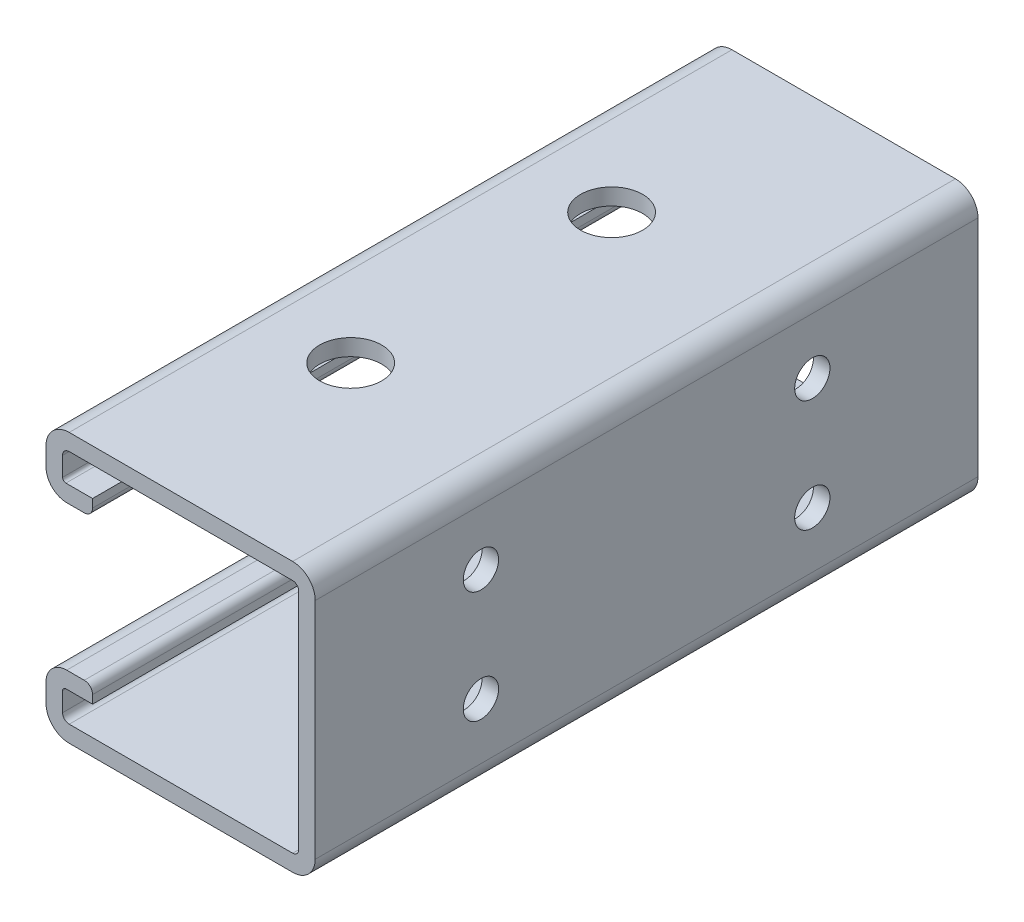
SolidWorks part; units mm, degrees
ref_plane "Front Plane" through (0, 0, 0) normal (0, 0, 1) x (1, 0, 0)
ref_plane "Top Plane" through (0, 0, 0) normal (0, 1, 0) x (1, 0, 0)
ref_plane "Right Plane" through (0, 0, 0) normal (1, 0, 0) x (0, 0, -1)
sketch "Sketch1" plane through (0, 0, 0) normal (0, 0, 1) x (1, 0, 0)
  line L0 (20.6375, 0) -> (-20.6375, 0) construction
  line L3 (-20.6375, 20.6375) -> (20.6375, 20.6375) construction
  line L4 (-20.6375, 20.6375) -> (-20.6375, -20.6375) construction
  line L5 (-20.6375, -20.6375) -> (20.6375, -20.6375) construction
  line L6 (20.6375, 20.6375) -> (20.6375, -20.6375) construction
  line L7 (-17.0815, 20.6375) -> (17.1768, 20.6375)
  line L8 (20.6375, 17.1767) -> (20.6375, -17.1767)
  line L9 (18.0975, -17.1767) -> (18.0975, 17.1767)
  line L10 (17.1768, 18.0975) -> (-17.0815, 18.0975)
  line L11 (-20.6375, 17.0815) -> (-20.6375, 14.2875)
  line L12 (-17.4625, 11.1125) -> (-14.7701, 11.1125)
  line L14 (-13.5001, 13.6525) -> (-17.5895, 13.6525)
  line L15 (-18.0975, 14.1605) -> (-18.0975, 17.0815)
  line L16 (-18.0975, -14.1605) -> (-18.0975, -17.0815)
  line L17 (-13.5001, -13.6525) -> (-17.5895, -13.6525)
  line L18 (-17.4625, -11.1125) -> (-14.7701, -11.1125)
  line L19 (-20.6375, -17.0815) -> (-20.6375, -14.2875)
  line L20 (17.1768, -18.0975) -> (-17.0815, -18.0975)
  line L21 (-17.0815, -20.6375) -> (17.1768, -20.6375)
  line L22 (18.0975, -20.6375) -> (18.0975, 20.6375) construction
  line L23 (-13.5001, 13.6525) -> (-13.5001, 12.3825)
  line L24 (-13.5001, 12.3825) -> (-13.5001, 11.1125) construction
  line L25 (-13.5001, -13.6525) -> (-13.5001, -12.3825)
  line L26 (0.0476, 18.0975) -> (0.0476, -18.0975) construction
  arc A1 (20.6375, 17.1767) -> (17.1768, 20.6375) centre (17.1768, 17.1767) ccw
  arc A2 (18.0975, 17.1767) -> (17.1768, 18.0975) centre (17.1768, 17.1767) ccw
  arc A4 (-17.0815, 20.6375) -> (-20.6375, 17.0815) centre (-17.0815, 17.0815) ccw
  arc A5 (-20.6375, 14.2875) -> (-17.4625, 11.1125) centre (-17.4625, 14.2875) ccw
  arc A6 (-13.5001, 12.3825) -> (-14.7701, 11.1125) centre (-14.7701, 12.3825) cw
  arc A7 (-17.5895, 13.6525) -> (-18.0975, 14.1605) centre (-17.5895, 14.1605) cw
  arc A8 (-18.0975, 17.0815) -> (-17.0815, 18.0975) centre (-17.0815, 17.0815) cw
  arc A9 (-18.0975, -17.0815) -> (-17.0815, -18.0975) centre (-17.0815, -17.0815) ccw
  arc A10 (-17.5895, -13.6525) -> (-18.0975, -14.1605) centre (-17.5895, -14.1605) ccw
  arc A11 (-13.5001, -12.3825) -> (-14.7701, -11.1125) centre (-14.7701, -12.3825) ccw
  arc A12 (-20.6375, -14.2875) -> (-17.4625, -11.1125) centre (-17.4625, -14.2875) cw
  arc A13 (-17.0815, -20.6375) -> (-20.6375, -17.0815) centre (-17.0815, -17.0815) cw
  arc A14 (18.0975, -17.1767) -> (17.1768, -18.0975) centre (17.1768, -17.1767) cw
  arc A15 (20.6375, -17.1767) -> (17.1768, -20.6375) centre (17.1768, -17.1767) cw
  point P24 (20.6375, 20.6375)
  point P65 (18.0975, 0)
  dimension "D1" = 3.4608
  dimension "D2" = 3.556
  dimension "D3" = 3.175
  dimension "D5" = 0.508
  dimension "Channel Height" = 41.275
  dimension "Channel Width" = 41.275
  dimension "Thickness" = 2.54
  dimension "Inside Channel Width" = 22.225
  dimension "D4" = 7.1374
  dimension "D6" = 2.54
  dimension "D7" = 3.5814
  dimension "D8" = 36.195
sketch "Sketch3" plane through (0, 0, 0) normal (1, 0, 0) x (0, 0, -1)
  line L0 (-152.4, 0) -> (152.4, 0) construction
  point P2 (-69.85, 0)
  point P3 (69.85, 0)
  dimension "D1" = 82.55
  dimension "D2" = 82.55
  dimension "Length" = 304.8
sketch "Sketch4" plane through (0, 0, 0) normal (0, 0, 1) x (1, 0, 0)
  line L16 (-17.0815, -20.6375) -> (17.1768, -20.6375)
  line L17 (-20.6375, -14.2875) -> (-20.6375, -17.0815)
  line L18 (-14.7701, -11.1125) -> (-17.4625, -11.1125)
  line L19 (-13.5001, -13.6525) -> (-13.5001, -12.3825)
  line L20 (-17.5895, -13.6525) -> (-13.5001, -13.6525)
  line L21 (-18.0975, -17.0815) -> (-18.0975, -14.1605)
  line L22 (17.1768, -18.0975) -> (-17.0815, -18.0975)
  line L23 (18.0975, 17.1767) -> (18.0975, -17.1767)
  line L24 (-17.0815, 18.0975) -> (17.1768, 18.0975)
  line L25 (-18.0975, 14.1605) -> (-18.0975, 17.0815)
  line L26 (-13.5001, 13.6525) -> (-17.5895, 13.6525)
  line L27 (-13.5001, 12.3825) -> (-13.5001, 13.6525)
  line L28 (-17.4625, 11.1125) -> (-14.7701, 11.1125)
  line L29 (-20.6375, 17.0815) -> (-20.6375, 14.2875)
  line L30 (17.1768, 20.6375) -> (-17.0815, 20.6375)
  line L31 (20.6375, -17.1767) -> (20.6375, 17.1767)
  line L32 (-17.0815, -20.6375) -> (17.1768, -20.6375)
  line L33 (-20.6375, -14.2875) -> (-20.6375, -17.0815)
  line L34 (-14.7701, -11.1125) -> (-17.4625, -11.1125)
  line L35 (-13.5001, -13.6525) -> (-13.5001, -12.3825)
  line L36 (-17.5895, -13.6525) -> (-13.5001, -13.6525)
  line L37 (-18.0975, -17.0815) -> (-18.0975, -14.1605)
  line L38 (17.1768, -18.0975) -> (-17.0815, -18.0975)
  line L39 (18.0975, 17.1767) -> (18.0975, -17.1767)
  line L40 (-17.0815, 18.0975) -> (17.1768, 18.0975)
  line L41 (-18.0975, 14.1605) -> (-18.0975, 17.0815)
  line L42 (-13.5001, 13.6525) -> (-17.5895, 13.6525)
  line L43 (-13.5001, 12.3825) -> (-13.5001, 13.6525)
  line L44 (-17.4625, 11.1125) -> (-14.7701, 11.1125)
  line L45 (-20.6375, 17.0815) -> (-20.6375, 14.2875)
  line L46 (17.1768, 20.6375) -> (-17.0815, 20.6375)
  line L47 (20.6375, -17.1767) -> (20.6375, 17.1767)
  arc A14 (-20.6375, -17.0815) -> (-17.0815, -20.6375) centre (-17.0815, -17.0815) ccw
  arc A15 (-17.4625, -11.1125) -> (-20.6375, -14.2875) centre (-17.4625, -14.2875) ccw
  arc A16 (-13.5001, -12.3825) -> (-14.7701, -11.1125) centre (-14.7701, -12.3825) ccw
  arc A17 (-17.5895, -13.6525) -> (-18.0975, -14.1605) centre (-17.5895, -14.1605) ccw
  arc A18 (-18.0975, -17.0815) -> (-17.0815, -18.0975) centre (-17.0815, -17.0815) ccw
  arc A19 (17.1768, -18.0975) -> (18.0975, -17.1767) centre (17.1768, -17.1767) ccw
  arc A20 (18.0975, 17.1767) -> (17.1768, 18.0975) centre (17.1768, 17.1767) ccw
  arc A21 (-17.0815, 18.0975) -> (-18.0975, 17.0815) centre (-17.0815, 17.0815) ccw
  arc A22 (-18.0975, 14.1605) -> (-17.5895, 13.6525) centre (-17.5895, 14.1605) ccw
  arc A23 (-14.7701, 11.1125) -> (-13.5001, 12.3825) centre (-14.7701, 12.3825) ccw
  arc A24 (-20.6375, 14.2875) -> (-17.4625, 11.1125) centre (-17.4625, 14.2875) ccw
  arc A25 (-17.0815, 20.6375) -> (-20.6375, 17.0815) centre (-17.0815, 17.0815) ccw
  arc A26 (20.6375, 17.1767) -> (17.1768, 20.6375) centre (17.1768, 17.1767) ccw
  arc A27 (17.1768, -20.6375) -> (20.6375, -17.1767) centre (17.1768, -17.1767) ccw
  arc A28 (-20.6375, -17.0815) -> (-17.0815, -20.6375) centre (-17.0815, -17.0815) ccw
  arc A29 (-17.4625, -11.1125) -> (-20.6375, -14.2875) centre (-17.4625, -14.2875) ccw
  arc A30 (-13.5001, -12.3825) -> (-14.7701, -11.1125) centre (-14.7701, -12.3825) ccw
  arc A31 (-17.5895, -13.6525) -> (-18.0975, -14.1605) centre (-17.5895, -14.1605) ccw
  arc A32 (-18.0975, -17.0815) -> (-17.0815, -18.0975) centre (-17.0815, -17.0815) ccw
  arc A33 (17.1768, -18.0975) -> (18.0975, -17.1767) centre (17.1768, -17.1767) ccw
  arc A34 (18.0975, 17.1767) -> (17.1768, 18.0975) centre (17.1768, 17.1767) ccw
  arc A35 (-17.0815, 18.0975) -> (-18.0975, 17.0815) centre (-17.0815, 17.0815) ccw
  arc A36 (-18.0975, 14.1605) -> (-17.5895, 13.6525) centre (-17.5895, 14.1605) ccw
  arc A37 (-14.7701, 11.1125) -> (-13.5001, 12.3825) centre (-14.7701, 12.3825) ccw
  arc A38 (-20.6375, 14.2875) -> (-17.4625, 11.1125) centre (-17.4625, 14.2875) ccw
  arc A39 (-17.0815, 20.6375) -> (-20.6375, 17.0815) centre (-17.0815, 17.0815) ccw
  arc A40 (20.6375, 17.1767) -> (17.1768, 20.6375) centre (17.1768, 17.1767) ccw
  arc A41 (17.1768, -20.6375) -> (20.6375, -17.1767) centre (17.1768, -17.1767) ccw
  dimension "D1" = 0
extrude "Boss-Extrude1" add sketch "Sketch4" along normal blind 50.8 and the other way blind 50.8
sketch "Sketch7" plane through (0, 20.6375, 0) normal (0, 1, 0) x (1, 0, 0)
  line L0 (17.1768, 0) -> (-17.0815, 0) construction
  line L1 (17.1768, 50.8) -> (17.1768, -50.8) construction
  line L2 (-17.0815, 50.8) -> (-17.0815, -50.8) construction
  line L3 (0.0476, 50.8) -> (0.0476, -50.8) construction
  line L4 (17.1768, 50.8) -> (-17.0815, 50.8) construction
  line L5 (17.1768, -50.8) -> (-17.0815, -50.8) construction
  circle A0 centre (-4.7307, -20) radius 4.7625
  circle A1 centre (-4.7308, 20) radius 4.7625
  point P6 (-4.7307, -20)
  dimension "D3" = 9.525
  dimension "D1" = 20
  dimension "D2" = 21.9075
extrude "Cut-Extrude1" cut sketch "Sketch7" against normal blind 45.72
sketch "Sketch8" plane through (20.6375, 0, 0) normal (1, 0, 0) x (0, 0, -1)
  line L0 (0, 0) -> (0, -17.1767) construction
  line L1 (-50.8, -17.1767) -> (50.8, -17.1767) construction
  line L2 (-50.8, -17.1767) -> (-50.8, 17.1767) construction
  line L3 (-50.8, 17.1767) -> (50.8, 17.1767) construction
  line L4 (50.8, -17.1767) -> (50.8, 17.1767) construction
  line L5 (-50.8, -17.1767) -> (50.8, 17.1767) construction
  line L6 (-50.8, 17.1767) -> (50.8, -17.1767) construction
  line L7 (0, 0) -> (50.8, 0) construction
  line L8 (25.4, 0) -> (25.4, -17.1767) construction
  line L9 (0, -8.5884) -> (50.8, -8.5884) construction
  circle A0 centre (25.4, -8.5884) radius 2.7051
  circle A1 centre (25.4, 8.5884) radius 2.7051
  circle A2 centre (-25.4, -8.5884) radius 2.7051
  circle A3 centre (-25.4, 8.5884) radius 2.7051
  point P0 (0, 0)
  dimension "D1" = 5.4102
  dimension "D2" = 34.3535
  dimension "D3" = 8.5884
  dimension "D4" = 25.4
extrude "Cut-Extrude2" cut sketch "Sketch8" against normal up to surface (2.54 mm away) up to face at (18.0975, 0, 0)
equation "\"D1@Sketch3\" = \"Channel Height@Sketch1\" * 2"
equation "\"D2@Sketch3\"=\"D1@Sketch3\""
equation "\"D6@Sketch1\"=\"Thickness@Sketch1\""
